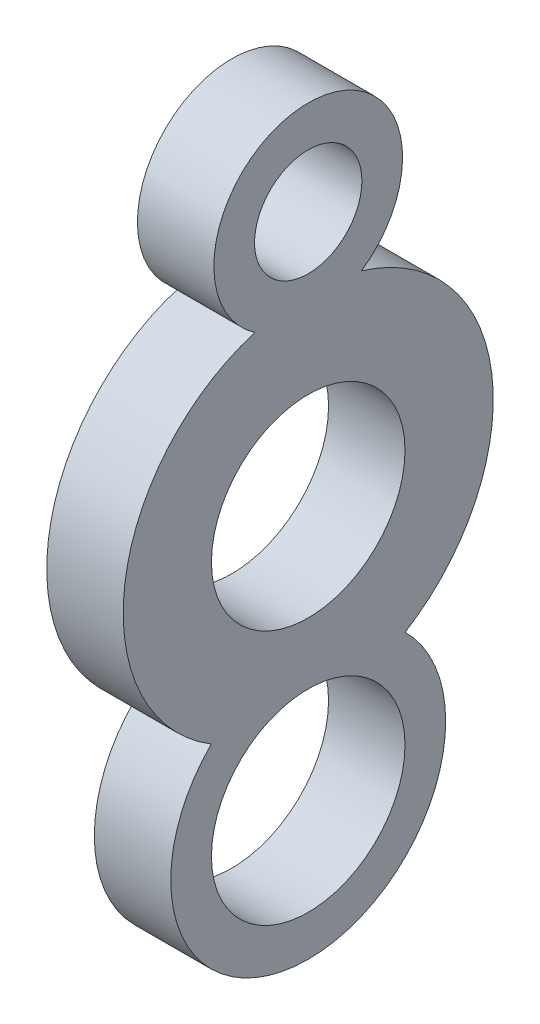
SolidWorks part; units mm, degrees
ref_plane "Front Plane" through (0, 0, 0) normal (0, 0, 1) x (1, 0, 0)
ref_plane "Top Plane" through (0, 0, 0) normal (0, 1, 0) x (1, 0, 0)
ref_plane "Right Plane" through (0, 0, 0) normal (1, 0, 0) x (0, 0, -1)
sketch "Sketch1" plane through (0, 0, 0) normal (1, 0, 0) x (0, 0, -1)
  line L0 (0, 79.629) -> (0, -79.629) construction
  circle A0 centre (0, -79.629) radius 30.226
  circle A1 centre (0, 79.629) radius 16.764
  circle A2 centre (0, 0) radius 30.226
  circle A3 centre (0, 0) radius 45.085
  circle A4 centre (0, 79.629) radius 29.464
  circle A5 centre (0, 0) radius 57.785
  circle A6 centre (0, -79.629) radius 42.926
  point P0 (0, 0)
  dimension "D2" = 33.528
  dimension "D3" = 60.452
  dimension "D4" = 60.452
  dimension "D5" = 90.17
  dimension "D6" = 12.7
  dimension "D1" = 159.258
extrude "Boss-Extrude1" add sketch "Sketch1" along normal blind 23.876 contours A1 A5 A4 | A5 L0 A4 | L0 A5 A4 | L0 A4 A5 A6 A3 | A3 L0 A2 A6 | A4 L0 A3 A6 A5 | L0 A3 A6 A2 | L0 A3 A6 A5 A0 | A3 L0 A0 A5 A6 | A6 L0 A3 | L0 A6 A3 | A5 A6 A0 region at (0, 57.9571, 8.5382) region at (0, 54.2259, -6.3093) region at (0, 54.2259, 6.3093) region at (0, 50.3449, -9.0767) region at (0, 47.625, 1.1945) region at (0, 31.1927, -31.1927) region at (0, 37.6555, 0.9718) region at (0, -47.9012, 15.7255) region at (0, -53.5395, 24.5846) region at (0, -40.9151, 7.0729) region at (0, -47.9012, -15.7255) region at (0, -40.9151, -7.0729)
